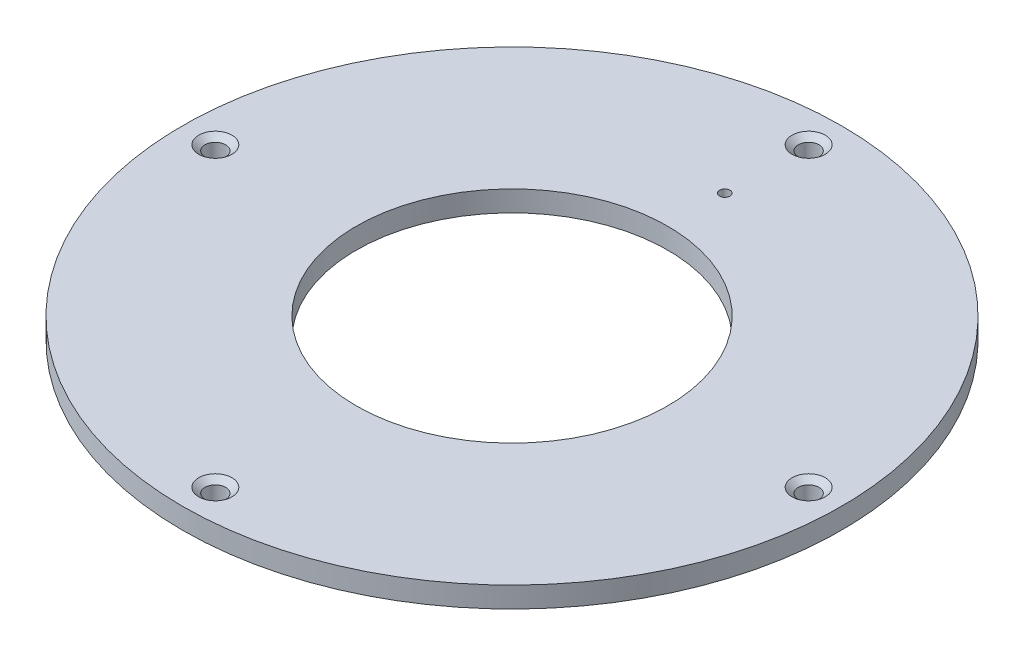
SolidWorks part; units mm, degrees
material "1060 Alloy"
ref_plane "Front Plane" through (0, 0, 0) normal (0, 0, 1) x (1, 0, 0)
ref_plane "Top Plane" through (0, 0, 0) normal (0, 1, 0) x (1, 0, 0)
ref_plane "Right Plane" through (0, 0, 0) normal (1, 0, 0) x (0, 0, -1)
sketch "Sketch1" plane through (0, 0, 0) normal (0, 1, 0) x (1, 0, 0)
  circle A0 centre (0, 0) radius 15.875
  dimension "D1" = 31.75
extrude "Boss-Extrude1" add sketch "Sketch1" along normal blind 1
sketch "Sketch2" plane through (0, 1, 0) normal (0, 1, 0) x (1, 0, 0)
  circle A0 centre (0, 0) radius 7.5
  dimension "D1" = 15
extrude "Cut-Extrude1" cut sketch "Sketch2" against normal through all both and the other way through all
ref_plane "Plane2" through (0, 0.5, 0) normal (0, 1, 0) x (1, 0, 0)
sketch "Sketch4" plane through (0, 1, 0) normal (0, 1, 0) x (1, 0, 0)
  circle A0 centre (0, 10.25) radius 0.25
  dimension "D1" = 0.5
  dimension "D2" = 10.25
extrude "Cut-Extrude2" cut sketch "Sketch4" against normal through all both and the other way through all
hole_wizard "CSK for M2 Flat Head Machine Screw1" positions "Sketch5" profile "Sketch6" countersink size "M2" standard "ANSI Metric" end condition through all
sketch "Sketch5" plane through (0, 1, 0) normal (0, 1, 0) x (1, 0, 0)
  point P0 (0, 14.29)
  point P2 (14.29, 0)
  point P4 (0, -14.29)
  point P6 (-14.29, 0)
  dimension "D1" = 14.29
  dimension "D2" = 14.29
  dimension "D3" = 14.29
  dimension "D4" = 14.29
sketch "Sketch6" plane through (0, 1, -14.29) normal (1, 0, 0) x (0, 0, 1)
  line L0 (0, 0) -> (0, 1)
  line L1 (0, 1) -> (0.5, 1)
  line L2 (0.5, 1) -> (0.5, 0.2517)
  line L3 (0.5, 0.2517) -> (0.8, 0)
  line L5 (0.8, 0) -> (0, 0)
  line L6 (-0.5, 0.2517) -> (-0.8, 0) construction
  line L11 (0, -6.35) -> (0, 107.95) construction
  dimension "Thru Hole Dia." = 1
  dimension "Thru Hole Depth" = 1
  dimension "Near C'Sink Dia." = 1.6
  dimension "Near C'Sink Angle" = 100
